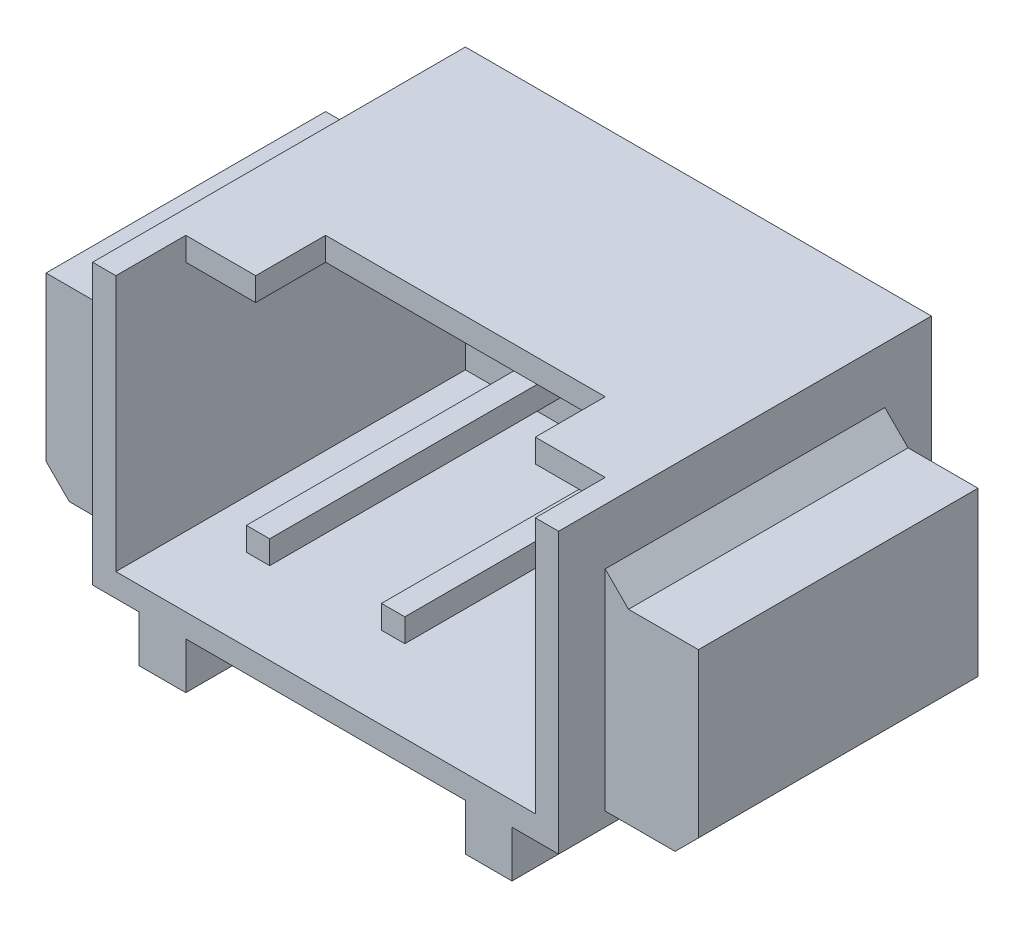
SolidWorks part; units mm, degrees
ref_plane "Front Plane" through (0, 0, 0) normal (0, 0, 1) x (1, 0, 0)
ref_plane "Top Plane" through (0, 0, 0) normal (0, 1, 0) x (1, 0, 0)
ref_plane "Right Plane" through (0, 0, 0) normal (1, 0, 0) x (0, 0, -1)
sketch "Sketch1" plane through (0, 0, 0) normal (0, 0, 1) x (1, 0, 0)
  line L1 (0, 0) -> (-2.5, 0)
  line L2 (0, 0) -> (0, 3)
  line L3 (0, 3) -> (-2.5, 3)
  line L4 (-2.5, 0) -> (-2.5, 3)
  line L5 (-2.5, 2.15) -> (-3.5, 2.15)
  line L6 (-2.5, 2.15) -> (-2.5, 0.15)
  line L7 (-2.5, 0.15) -> (-3.5, 0.15)
  line L8 (-3.5, 2.15) -> (-3.5, 0.15)
  line L9 (-2, 0) -> (-1.5, 0)
  line L10 (-2, 0) -> (-2, -0.5)
  line L11 (-2, -0.5) -> (-1.5, -0.5)
  line L12 (-1.5, 0) -> (-1.5, -0.5)
  dimension "D1" = 2.5
  dimension "D2" = 0.5
  dimension "D3" = 0.5
  dimension "D4" = 0.5
  dimension "D5" = 0.15
  dimension "D6" = 1
  dimension "D7" = 2
  dimension "D8" = 3
extrude "Boss-Extrude1" add sketch "Sketch1" along normal mid plane 4 contours L4 L1 L2 L3 | L10 L9 L12 L11 region at (-1.25, 1.5, 0)
extrude "Boss-Extrude2" add sketch "Sketch1<3>" along normal mid plane 3 contours L5 L8 L7 L4 region at (-3, 1.15, 0)
sketch "Sketch1<3>" plane through (0, 0, 0) normal (0, 0, 1) x (1, 0, 0) same geometry as "Sketch1"
chamfer "Chamfer1" distance 0.25 angle 45 2 edges at (-3.5, 0.15, 0) (-2.5, 2.15, 0)
sketch "Sketch2" plane through (0, 0, 2) normal (0, 0, 1) x (1, 0, 0)
  line L0 (0, 0) -> (-1.5, 0) construction
  line L1 (-0.6, 1.13) -> (-0.85, 1.13)
  line L2 (-0.6, 1.13) -> (-0.6, 1.38)
  line L3 (-0.6, 1.38) -> (-0.85, 1.38)
  line L4 (-0.85, 1.13) -> (-0.85, 1.38)
  line L5 (0, 0) -> (0, 3) construction
  line L11 (-2.25, 0.25) -> (0, 0.25)
  line L12 (-2.25, 2.75) -> (0, 2.75)
  line L13 (-2.25, 0) -> (-2.25, 2.75)
  line L14 (-2.25, 2.75) -> (0, 2.75)
  line L15 (-2.25, 0.25) -> (-2.25, 2.75)
  line L16 (0, 2.75) -> (0, 0.25)
  point P6 (-0.75, 0)
  dimension "D1" = 0.25
  dimension "D2" = 0.25
  dimension "D3" = 1.13
  dimension "D4" = 0.6
  dimension "D6" = 0.25
  dimension "D5" = 0.25
extrude "Cut-Extrude1" cut sketch "Sketch2" against normal blind 3.75
sketch "Sketch3" plane through (0, 3, 0) normal (0, 1, 0) x (1, 0, 0)
  line L0 (-2.25, -2) -> (-1.5, -2)
  line L1 (0, -2) -> (-1.5, -2)
  line L2 (0, -2) -> (0, -0.5)
  line L3 (0, -0.5) -> (-1.5, -0.5)
  line L4 (-1.5, -2) -> (-1.5, -0.5)
  line L5 (-1.5, -2) -> (-2.25, -2)
  line L6 (-1.5, -2) -> (-1.5, -1.25)
  line L7 (-1.5, -1.25) -> (-2.25, -1.25)
  line L8 (-2.25, -2) -> (-2.25, -1.25)
  dimension "D1" = 1.5
  dimension "D2" = 0.75
  dimension "D3" = 0.75
  dimension "D4" = 0.75
extrude "Cut-Extrude2" cut sketch "Sketch3" against normal up to next contours L2 L1 L4 L3 | L6 L5 L8 L7
mirror "Mirror1" about plane through (0, 0, 2) normal (-1, 0, 0) of bodies 104
